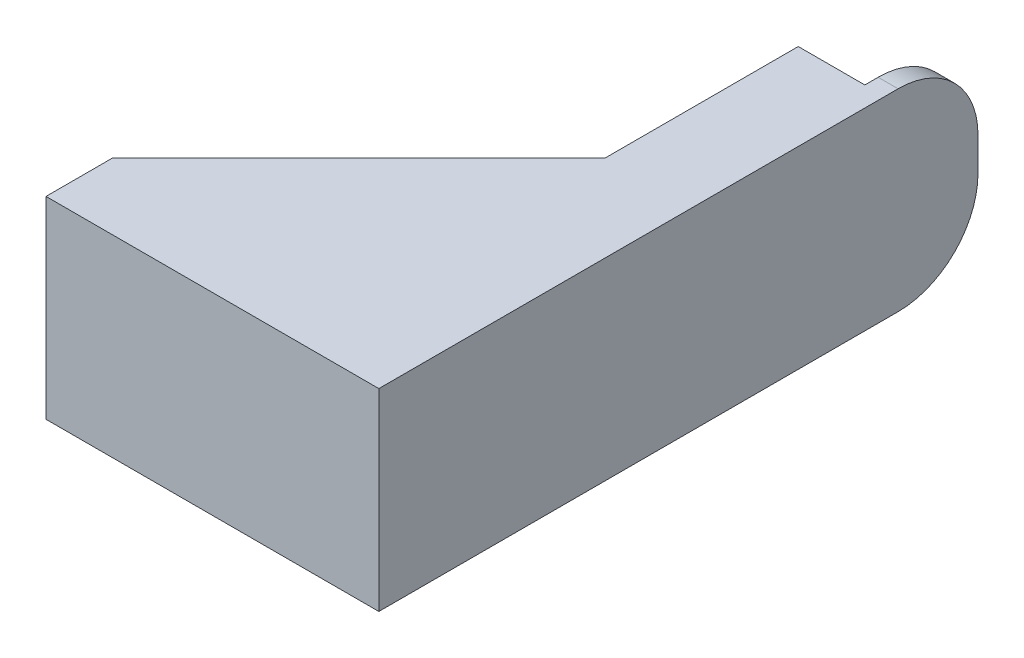
SolidWorks part; units mm, degrees
ref_plane "Front Plane" through (0, 0, 0) normal (0, 0, 1) x (1, 0, 0)
ref_plane "Top Plane" through (0, 0, 0) normal (0, 1, 0) x (1, 0, 0)
ref_plane "Right Plane" through (0, 0, 0) normal (1, 0, 0) x (0, 0, -1)
sketch "Sketch1" plane through (0, 0, 0) normal (0, 0, 1) x (1, 0, 0)
  line L0 (-50, 0) -> (0, 0) construction
  line L1 (0, -14.5) -> (-50, -14.5)
  line L2 (0, -14.5) -> (0, 14.5)
  line L3 (0, 14.5) -> (-50, 14.5)
  line L4 (-50, -14.5) -> (-50, 14.5)
  line L5 (0, 0) -> (-50, 0) construction
  dimension "D1" = 29
  dimension "D2" = 50
extrude "Boss-Extrude1" add sketch "Sketch1" against normal blind 50
sketch "Sketch2" plane through (0, 0, -50) normal (0, 0, -1) x (-1, 0, 0)
  line L0 (0, 14.5) -> (50, 14.5) construction
  line L1 (0, -14.5) -> (13, -14.5)
  line L2 (0, -14.5) -> (0, 14.5)
  line L3 (0, 14.5) -> (13, 14.5)
  line L4 (13, -14.5) -> (13, 14.5)
  dimension "D1" = 13
extrude "Boss-Extrude2" add sketch "Sketch2" along normal blind 40
chamfer "Chamfer1" distance 40 angle 45 1 edges at (-50, 0, -50)
sketch "Sketch3" plane through (0, 0, -90) normal (0, 0, -1) x (-1, 0, 0)
  line L0 (0, -14.5) -> (13, -14.5) construction
  line L1 (13, 14.5) -> (3, 14.5)
  line L2 (13, 14.5) -> (13, -14.5)
  line L3 (13, -14.5) -> (3, -14.5)
  line L4 (3, 14.5) -> (3, -14.5)
  line L5 (0, 14.5) -> (0, -14.5) construction
  dimension "D1" = 3
extrude "Cut-Extrude1" cut sketch "Sketch3" against normal blind 14
fillet "Fillet1" radius 12 2 edges at (-1.5, 14.5, -90) (-1.5, -14.5, -90)
